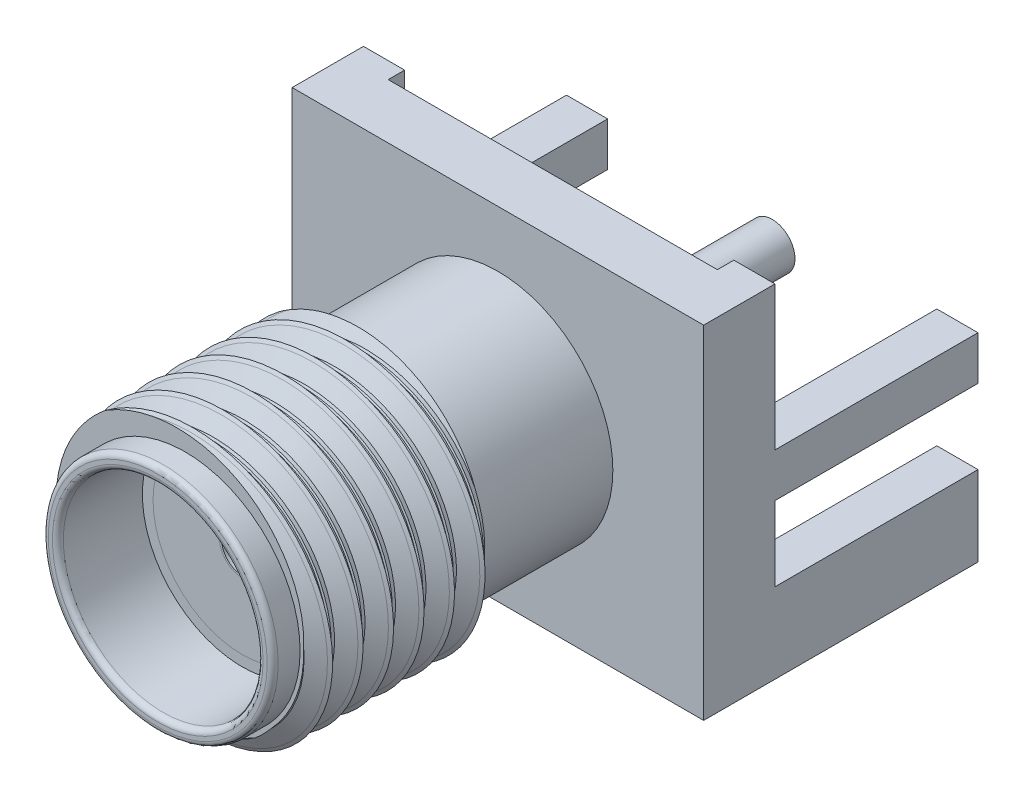
SolidWorks part; units mm, degrees
material "Brass"
ref_plane "Front Plane" through (0, 0, 0) normal (0, 0, 1) x (1, 0, 0)
ref_plane "Top Plane" through (0, 0, 0) normal (0, 1, 0) x (1, 0, 0)
ref_plane "Right Plane" through (0, 0, 0) normal (1, 0, 0) x (0, 0, -1)
sketch "Sketch1" plane through (0, 0, 0) normal (0, 0, 1) x (1, 0, 0)
  circle A0 centre (0, 0) radius 2.6607
  dimension "D1" = 5.3213
extrude "Boss-Extrude1" add sketch "Sketch1" along normal blind 7.874
sketch "Sketch2" plane through (0, 0, 7.874) normal (0, 0, 1) x (1, 0, 0)
  circle A0 centre (0, 0) radius 2.3114
  dimension "D1" = 4.6228
extrude "Cut-Extrude1" cut sketch "Sketch2" against normal blind 1.9558
sketch "Sketch5" plane through (0, 0, 0) normal (0, 0, -1) x (-1, 0, 0)
  line L0 (0, 2.6607) -> (0, 3.9624) construction
  line L1 (-4.7625, 3.9624) -> (4.7625, 3.9624)
  line L2 (-4.7625, 3.9624) -> (-4.7625, -3.9624)
  line L3 (-4.7625, -3.9624) -> (4.7625, -3.9624)
  line L4 (4.7625, 3.9624) -> (4.7625, -3.9624)
  line L5 (2.6607, 0) -> (4.7625, 0) construction
  circle A0 centre (0, 0) radius 2.6607 construction
  circle A1 centre (0, 0) radius 2.6607 construction
  circle A2 centre (0, 0) radius 2.032
  dimension "D3" = 4.064
  dimension "D1" = 9.525
  dimension "D2" = 7.9248
extrude "Boss-Extrude2" add sketch "Sketch5" along normal blind 1.651 separate body
sketch "Sketch6" plane through (0, 3.9624, 0) normal (0, 1, 0) x (1, 0, 0)
  line L0 (-4.7625, 1.651) -> (4.7625, 1.651) construction
  line L1 (-3.81, 1.651) -> (3.81, 1.651)
  line L2 (-3.81, 1.651) -> (-3.81, 1.27)
  line L3 (-3.81, 1.27) -> (3.81, 1.27)
  line L4 (3.81, 1.651) -> (3.81, 1.27)
  line L5 (-4.7625, 0) -> (4.7625, 0) construction
  line L6 (0, 1.27) -> (0, 0) construction
  dimension "D1" = 1.27
  dimension "D2" = 7.62
extrude "Cut-Extrude2" cut sketch "Sketch6" against normal through all
sketch "Sketch7" plane through (0, 0, 5.9182) normal (0, 0, 1) x (1, 0, 0)
  circle A0 centre (0, 0) radius 0.4763
  dimension "D1" = 0.9525
extrude "Cut-Extrude3" cut sketch "Sketch7" against normal through all
sketch "Sketch8" plane through (0, 0, 5.9182) normal (0, 0, 1) x (1, 0, 0)
  circle A0 centre (0, 0) radius 2.0638
  circle A4 centre (0, 0) radius 0.5259
  circle A5 centre (0, 0) radius 0.5259
  dimension "D1" = 4.1275
  dimension "D2" = 0.0496
split line "Split Line1"
sketch "Sketch9" plane through (0, 0, 0) normal (0, 0, 1) x (1, 0, 0)
  circle A0 centre (0, 0) radius 0.5259 construction
  circle A1 centre (0, 0) radius 0.5259
extrude "Boss-Extrude4" add sketch "Sketch9" against normal offset from surface (6.35 mm away) 5.08 separate body up to face at (2.032, 0, -1.27) offset beyond the face yes
sketch "Sketch10" plane through (0, 0, -1.651) normal (0, 0, -1) x (-1, 0, 0)
  line L0 (3.81, -3.9624) -> (3.81, 3.9624) construction
  line L1 (3.81, 0.635) -> (4.7625, 0.635)
  line L2 (3.81, 0.635) -> (3.81, -0.381)
  line L3 (3.81, -0.381) -> (4.7625, -0.381)
  line L4 (4.7625, 0.635) -> (4.7625, -0.381)
  line L5 (4.7625, -3.9624) -> (4.7625, 3.9624) construction
  line L7 (3.81, -2.1082) -> (4.7625, -2.1082)
  line L8 (3.81, -2.1082) -> (3.81, -3.9624)
  line L9 (3.81, -3.9624) -> (4.7625, -3.9624)
  line L10 (4.7625, -2.1082) -> (4.7625, -3.9624)
  line L11 (3.81, -3.9624) -> (4.7625, -3.9624) construction
  line L12 (0, -1000) -> (0, 49000) construction
  line L13 (-4.7625, -2.1082) -> (-4.7625, -3.9624)
  line L14 (-3.81, -3.9624) -> (-4.7625, -3.9624)
  line L15 (-3.81, -2.1082) -> (-3.81, -3.9624)
  line L16 (-3.81, -2.1082) -> (-4.7625, -2.1082)
  line L17 (-4.7625, 0.635) -> (-4.7625, -0.381)
  line L18 (-3.81, -0.381) -> (-4.7625, -0.381)
  line L19 (-3.81, 0.635) -> (-3.81, -0.381)
  line L20 (-3.81, 0.635) -> (-4.7625, 0.635)
  dimension "D1" = 1.016
  dimension "D2" = 1.7272
  dimension "D3" = 1.8542
extrude "Boss-Extrude5" add sketch "Sketch10" along normal up to surface (4.699 mm away) up to face at (0.5259, 0, -6.35)
sketch "Sketch12" plane through (0, 0, 7.874) normal (0, 0, 1) x (1, 0, 0)
  circle A1 centre (0, 0) radius 3.1636
  dimension "MajorDiameter" = 6.3271
sketch "Sketch13" plane through (0, 0, 7.874) normal (0, 0, 1) x (1, 0, 0)
  circle A0 centre (0, 0) radius 3.1636
  circle A1 centre (0, 0) radius 2.6607
  circle A2 centre (0, 0) radius 2.6607 construction
  dimension "MajorDiameter" = 6.3271
extrude "Boss-Extrude6" add sketch "Sketch13" against normal blind 4.191 from offset 0.635 offset against normal yes
curve "Helix/Spiral1" pitch 0.7056 height 7.0556 radius 3.1636 centre (0, 0, 7.874) axis (0, 0, -1) start towards (0, 1, 0) parameters "Pitch"=0.7056
sketch "Sketch15" plane through (0, 0, 0) normal (1, 0, 0) x (0, 0, -1)
  line L0 (-7.874, 3.1636) -> (-7.874, -3.1636) construction
  line L1 (-6.4629, 3.1636) -> (-7.1684, 3.1636) construction
  line L2 (-7.1684, 3.1636) -> (-7.874, 3.1636) construction
  line L3 (-10.4133, 2.7445) -> (0, 2.7445) construction
  line L4 (-10.4133, 2.7445) -> (-10.4133, -2.7445) construction
  line L5 (-7.874, 0) -> (-10.4133, 0) construction
  line L6 (0, 3.9624) -> (0, -3.9624) construction
  line L7 (-6.4629, 3.1636) -> (-5.7573, 3.1636) construction
  line L8 (-8.4915, 3.0883) -> (-8.4033, 3.0883) construction
  line L9 (-8.4033, 3.0883) -> (-8.2048, 2.7445)
  line L10 (-8.2048, 2.7445) -> (-8.1166, 2.7445)
  line L11 (-7.874, 2.6607) -> (-7.874, -2.6607) construction
  line L12 (-3.048, 3.1636) -> (-7.239, 3.1636) construction
  line L13 (-8.1166, 2.7445) -> (-7.9181, 3.0883)
  line L14 (-7.9181, 3.0883) -> (-7.8299, 3.0883) construction
  line L15 (-7.8299, 3.0883) -> (-7.6314, 2.7445)
  line L16 (-7.6314, 2.7445) -> (-7.5432, 2.7445)
  line L17 (-7.5432, 2.7445) -> (-7.3447, 3.0883)
  line L18 (-7.3447, 3.0883) -> (-7.2565, 3.0883) construction
  line L19 (-8.1607, 2.7445) -> (-8.1607, 3.9348) construction
  line L20 (-7.9181, 3.0883) -> (-8.4033, 3.0883) construction
  line L21 (-7.5873, 2.7445) -> (-7.5873, 3.9348) construction
  line L22 (-7.3447, 3.0883) -> (-7.8299, 3.0883) construction
  line L23 (-7.874, 3.1636) -> (-7.874, 3.9348) construction
  line L24 (-7.9181, 3.0883) -> (-7.874, 3.1636)
  line L25 (-7.874, 3.1636) -> (-7.8299, 3.0883)
  line L26 (-7.3447, 3.0883) -> (-7.3447, 4.147)
  line L27 (-7.3447, 4.147) -> (-8.4033, 4.147)
  line L28 (-8.4033, 4.147) -> (-8.4033, 3.0883)
  spline S0 degree 3 poles (30.3197, -1996.2874) (-9.6986, -238.0579) (-8.6725, 16.4609) (-7.7858, 2.2952) (-7.7417, 1.2422) (-7.6976, 0) (-7.6535, -1.2422) (-7.6094, -2.2952) (-7.5653, -2.9988) (-7.5212, -3.2459) (-7.4771, -2.9988) (-7.433, -2.2952) (-7.3889, -1.2422) (-7.3448, 0) (-7.3007, 1.2422) (-7.2566, 2.2952) (-7.2125, 2.9988) (-7.1684, 3.2459) (-7.1243, 2.9988) (-7.0803, 2.2952) (-7.0362, 1.2422) (-6.9921, 0) (-6.948, -1.2422) (-6.9039, -2.2952) (-6.8598, -2.9988) (-6.8157, -3.2459) (-6.7716, -2.9988) (-6.7275, -2.2952) (-6.6834, -1.2422) (-6.6393, 0) (-6.5952, 1.2422) (-6.5511, 2.2952) (-6.507, 2.9988) (-6.4629, 3.2459) (-6.4188, 2.9988) (-6.3747, 2.2952) (-6.3306, 1.2422) (-6.2865, 0) (-6.2424, -1.2422) (-6.1983, -2.2952) (-6.1542, -2.9988) (-6.1101, -3.2459) (-6.066, -2.9988) (-6.0219, -2.2952) (-5.9778, -1.2422) (-5.9337, 0) (-5.8896, 1.2422) (-5.8455, 2.2952) (-5.8014, 2.9988) (-5.7573, 3.2459) (-5.7132, 2.9988) (-5.6691, 2.2952) (-5.625, 1.2422) (-5.5809, 0) (-5.5368, -1.2422) (-5.4927, -2.2952) (-5.4487, -2.9988) (-5.4046, -3.2459) (-5.3605, -2.9988) (-5.3164, -2.2952) (-5.2723, -1.2422) (-5.2282, 0) (-5.1841, 1.2422) (-5.14, 2.2952) (-5.0959, 2.9988) (-5.0518, 3.2459) (-5.0077, 2.9988) (-4.9636, 2.2952) (-4.9195, 1.2422) (-4.8754, 0) (-4.8313, -1.2422) (-4.7872, -2.2952) (-4.7431, -2.9988) (-4.699, -3.2459) (-4.6549, -2.9988) (-4.6108, -2.2952) (-4.5667, -1.2422) (-4.5226, 0) (-4.4785, 1.2422) (-4.4344, 2.2952) (-4.3903, 2.9988) (-4.3462, 3.2459) (-4.3021, 2.9988) (-4.258, 2.2952) (-4.2139, 1.2422) (-4.1698, 0) (-4.1257, -1.2422) (-4.0816, -2.2952) (-4.0375, -2.9988) (-3.9934, -3.2459) (-3.9493, -2.9988) (-3.9052, -2.2952) (-3.8612, -1.2422) (-3.8171, 0) (-3.773, 1.2422) (-3.7289, 2.2952) (-3.6848, 2.9988) (-3.6407, 3.2459) (-3.5966, 2.9988) (-3.5525, 2.2952) (-3.5084, 1.2422) (-3.4643, 0) (-3.4202, -1.2422) (-3.3761, -2.2952) (-3.332, -2.9988) (-3.2879, -3.2459) (-3.2438, -2.9988) (-3.1997, -2.2952) (-3.1556, -1.2422) (-3.1115, 0) (-3.0674, 1.2422) (-3.0233, 2.2952) (-2.9792, 2.9988) (-2.9351, 3.2459) (-2.891, 2.9988) (-2.8469, 2.2952) (-2.8028, 1.2422) (-2.7587, 0) (-2.7146, -1.2422) (-2.6705, -2.2952) (-2.6264, -2.9988) (-2.5823, -3.2459) (-2.5382, -2.9988) (-2.4941, -2.2952) (-2.45, -1.2422) (-2.4059, 0) (-2.3618, 1.2422) (-2.3177, 2.2952) (-2.2737, 2.9988) (-2.2296, 3.2459) (-2.1855, 2.9988) (-2.1414, 2.2952) (-2.0973, 1.2422) (-2.0532, 0) (-2.0091, -1.2422) (-1.965, -2.2952) (-1.9209, -2.9988) (-1.8768, -3.2459) (-1.8327, -2.9988) (-1.7886, -2.2952) (-1.7445, -1.2422) (-1.7004, 0) (-1.6563, 1.2422) (-1.6122, 2.2952) (-1.5681, 2.9988) (-1.524, 3.2459) (-1.4799, 2.9988) (-1.4358, 2.2952) (-1.3917, 1.2422) (-1.3476, 0) (-1.3035, -1.2422) (-1.2594, -2.2952) (-1.2153, -2.9988) (-1.1712, -3.2459) (-1.1271, -2.9988) (-1.083, -2.2952) (-1.0389, -1.2422) (-0.9948, 0) (-0.9507, 1.2422) (-0.9066, 2.2952) (-0.02, 16.461) (1.0062, -238.0612) (-39.0129, -1996.3232) knots -0.358731 -0.358731 -0.358731 -0.358731 0.00625 0.0125 0.01875 0.025 0.03125 0.0375 0.04375 0.05 0.05625 0.0625 0.06875 0.075 0.08125 0.0875 0.09375 0.1 0.10625 0.1125 0.11875 0.125 0.13125 0.1375 0.14375 0.15 0.15625 0.1625 0.16875 0.175 0.18125 0.1875 0.19375 0.2 0.20625 0.2125 0.21875 0.225 0.23125 0.2375 0.24375 0.25 0.25625 0.2625 0.26875 0.275 0.28125 0.2875 0.29375 0.3 0.30625 0.3125 0.31875 0.325 0.33125 0.3375 0.34375 0.35 0.35625 0.3625 0.36875 0.375 0.38125 0.3875 0.39375 0.4 0.40625 0.4125 0.41875 0.425 0.43125 0.4375 0.44375 0.45 0.45625 0.4625 0.46875 0.475 0.48125 0.4875 0.49375 0.5 0.50625 0.5125 0.51875 0.525 0.53125 0.5375 0.54375 0.55 0.55625 0.5625 0.56875 0.575 0.58125 0.5875 0.59375 0.6 0.60625 0.6125 0.61875 0.625 0.63125 0.6375 0.64375 0.65 0.65625 0.6625 0.66875 0.675 0.68125 0.6875 0.69375 0.7 0.70625 0.7125 0.71875 0.725 0.73125 0.7375 0.74375 0.75 0.75625 0.7625 0.76875 0.775 0.78125 0.7875 0.79375 0.8 0.80625 0.8125 0.81875 0.825 0.83125 0.8375 0.84375 0.85 0.85625 0.8625 0.86875 0.875 0.88125 0.8875 0.89375 0.9 0.90625 0.9125 0.91875 0.925 0.93125 0.9375 0.94375 0.95 0.95625 0.9625 0.96875 0.975 0.98125 0.9875 0.99375 1.358734 1.358734 1.358734 1.358734 only from (-7.874, 3.1636) to (-0.8184, 3.1636) construction
  spline S1 degree 3 poles (-7.874, 3.1636) (-7.8594, 3.1636) (-7.8299, 2.9988) (-7.7858, 2.2952) (-7.7417, 1.2422) (-7.6976, 0) (-7.6535, -1.2422) (-7.6094, -2.2952) (-7.5653, -2.9988) (-7.5212, -3.2459) (-7.4771, -2.9988) (-7.433, -2.2952) (-7.3889, -1.2422) (-7.3448, 0) (-7.3007, 1.2422) (-7.2566, 2.2952) (-7.2125, 2.9988) (-7.1684, 3.2459) (-7.1243, 2.9988) (-7.0803, 2.2952) (-7.0362, 1.2422) (-6.9921, 0) (-6.948, -1.2422) (-6.9039, -2.2952) (-6.8598, -2.9988) (-6.8157, -3.2459) (-6.7716, -2.9988) (-6.7275, -2.2952) (-6.6834, -1.2422) (-6.6393, 0) (-6.5952, 1.2422) (-6.5511, 2.2952) (-6.507, 2.9988) (-6.4629, 3.2459) (-6.4188, 2.9988) (-6.3747, 2.2952) (-6.3306, 1.2422) (-6.2865, 0) (-6.2424, -1.2422) (-6.1983, -2.2952) (-6.1542, -2.9988) (-6.1101, -3.2459) (-6.066, -2.9988) (-6.0219, -2.2952) (-5.9778, -1.2422) (-5.9337, 0) (-5.8896, 1.2422) (-5.8455, 2.2952) (-5.8014, 2.9988) (-5.7573, 3.2459) (-5.7132, 2.9988) (-5.6691, 2.2952) (-5.625, 1.2422) (-5.5809, 0) (-5.5368, -1.2422) (-5.4927, -2.2952) (-5.4487, -2.9988) (-5.4046, -3.2459) (-5.3605, -2.9988) (-5.3164, -2.2952) (-5.2723, -1.2422) (-5.2282, 0) (-5.1841, 1.2422) (-5.14, 2.2952) (-5.0959, 2.9988) (-5.0518, 3.2459) (-5.0077, 2.9988) (-4.9636, 2.2952) (-4.9195, 1.2422) (-4.8754, 0) (-4.8313, -1.2422) (-4.7872, -2.2952) (-4.7431, -2.9988) (-4.699, -3.2459) (-4.6549, -2.9988) (-4.6108, -2.2952) (-4.5667, -1.2422) (-4.5226, 0) (-4.4785, 1.2422) (-4.4344, 2.2952) (-4.3903, 2.9988) (-4.3462, 3.2459) (-4.3021, 2.9988) (-4.258, 2.2952) (-4.2139, 1.2422) (-4.1698, 0) (-4.1257, -1.2422) (-4.0816, -2.2952) (-4.0375, -2.9988) (-3.9934, -3.2459) (-3.9493, -2.9988) (-3.9052, -2.2952) (-3.8612, -1.2422) (-3.8171, 0) (-3.773, 1.2422) (-3.7289, 2.2952) (-3.6848, 2.9988) (-3.6407, 3.2459) (-3.5966, 2.9988) (-3.5525, 2.2952) (-3.5084, 1.2422) (-3.4643, 0) (-3.4202, -1.2422) (-3.3761, -2.2952) (-3.332, -2.9988) (-3.2879, -3.2459) (-3.2438, -2.9988) (-3.1997, -2.2952) (-3.1556, -1.2422) (-3.1115, 0) (-3.0674, 1.2422) (-3.0233, 2.2952) (-2.9792, 2.9988) (-2.9351, 3.2459) (-2.891, 2.9988) (-2.8469, 2.2952) (-2.8028, 1.2422) (-2.7587, 0) (-2.7146, -1.2422) (-2.6705, -2.2952) (-2.6264, -2.9988) (-2.5823, -3.2459) (-2.5382, -2.9988) (-2.4941, -2.2952) (-2.45, -1.2422) (-2.4059, 0) (-2.3618, 1.2422) (-2.3177, 2.2952) (-2.2737, 2.9988) (-2.2296, 3.2459) (-2.1855, 2.9988) (-2.1414, 2.2952) (-2.0973, 1.2422) (-2.0532, 0) (-2.0091, -1.2422) (-1.965, -2.2952) (-1.9209, -2.9988) (-1.8768, -3.2459) (-1.8327, -2.9988) (-1.7886, -2.2952) (-1.7445, -1.2422) (-1.7004, 0) (-1.6563, 1.2422) (-1.6122, 2.2952) (-1.5681, 2.9988) (-1.524, 3.2459) (-1.4799, 2.9988) (-1.4358, 2.2952) (-1.3917, 1.2422) (-1.3476, 0) (-1.3035, -1.2422) (-1.2594, -2.2952) (-1.2153, -2.9988) (-1.1712, -3.2459) (-1.1271, -2.9988) (-1.083, -2.2952) (-1.0389, -1.2422) (-0.9948, 0) (-0.9507, 1.2422) (-0.9066, 2.2952) (-0.8626, 2.9988) (-0.833, 3.1636) (-0.8184, 3.1636) knots 0 0 0 0 0.00625 0.0125 0.01875 0.025 0.03125 0.0375 0.04375 0.05 0.05625 0.0625 0.06875 0.075 0.08125 0.0875 0.09375 0.1 0.10625 0.1125 0.11875 0.125 0.13125 0.1375 0.14375 0.15 0.15625 0.1625 0.16875 0.175 0.18125 0.1875 0.19375 0.2 0.20625 0.2125 0.21875 0.225 0.23125 0.2375 0.24375 0.25 0.25625 0.2625 0.26875 0.275 0.28125 0.2875 0.29375 0.3 0.30625 0.3125 0.31875 0.325 0.33125 0.3375 0.34375 0.35 0.35625 0.3625 0.36875 0.375 0.38125 0.3875 0.39375 0.4 0.40625 0.4125 0.41875 0.425 0.43125 0.4375 0.44375 0.45 0.45625 0.4625 0.46875 0.475 0.48125 0.4875 0.49375 0.5 0.50625 0.5125 0.51875 0.525 0.53125 0.5375 0.54375 0.55 0.55625 0.5625 0.56875 0.575 0.58125 0.5875 0.59375 0.6 0.60625 0.6125 0.61875 0.625 0.63125 0.6375 0.64375 0.65 0.65625 0.6625 0.66875 0.675 0.68125 0.6875 0.69375 0.7 0.70625 0.7125 0.71875 0.725 0.73125 0.7375 0.74375 0.75 0.75625 0.7625 0.76875 0.775 0.78125 0.7875 0.79375 0.8 0.80625 0.8125 0.81875 0.825 0.83125 0.8375 0.84375 0.85 0.85625 0.8625 0.86875 0.875 0.88125 0.8875 0.89375 0.9 0.90625 0.9125 0.91875 0.925 0.93125 0.9375 0.94375 0.95 0.95625 0.9625 0.96875 0.975 0.98125 0.9875 0.99375 1 1 1 1 construction
  point P29 (-8.1607, 3.0883)
  point P32 (-7.5873, 3.0883)
  point P33 (-7.874, 3.0883)
  dimension "D1" = 60
  dimension "D2" = 0.5734
  dimension "MajorDiameter" = 6.3271
  dimension "MinorDiameter" = 5.4889
  dimension "8thPitch" = 0.0882
sweep "Cut-Sweep5" cut profiles "Sketch15" path "Helix/Spiral1"
fillet "Fillet1" radius 0.127 2 edges at (2.3114, 0, 7.874) (2.6607, 0, 7.874)
equation "\"MajorDiameter\"= 0.2491"
equation "\"MinorDiameter\"= 0.2161"
equation "\"Theta\"= 60"
equation "\"Pitch\"= 1/36 "
equation "\"8thPitch\"= \"Pitch\"/8"
